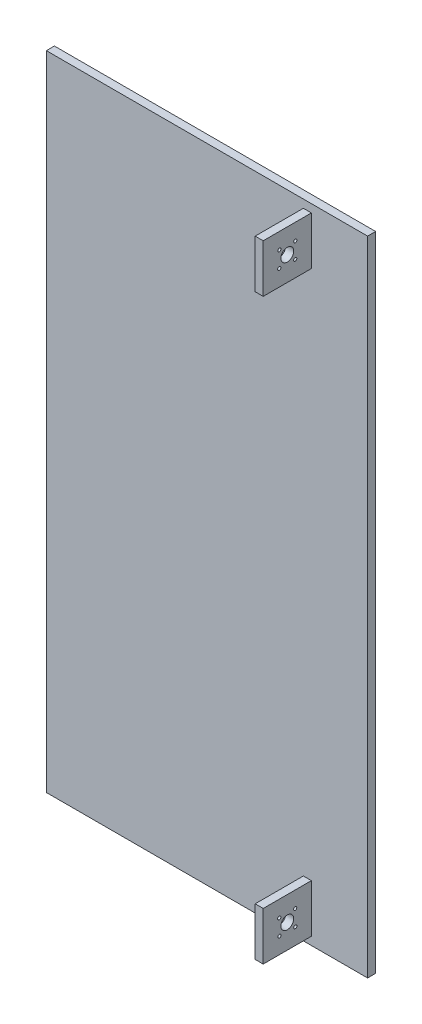
SolidWorks part; units mm, degrees
ref_plane "Plan de face" through (0, 0, 0) normal (0, 0, 1) x (1, 0, 0)
ref_plane "Plan de dessus" through (0, 0, 0) normal (0, 1, 0) x (1, 0, 0)
ref_plane "Plan de droite" through (0, 0, 0) normal (1, 0, 0) x (0, 0, -1)
sketch "Esquisse1" plane through (0, 0, 0) normal (0, 0, 1) x (1, 0, 0)
  line L5 (-100, -200) -> (100, -200)
  line L6 (-100, -200) -> (-100, 200)
  line L11 (-100, 200) -> (100, 200)
  line L12 (100, -200) -> (100, 200)
  line L13 (-100, -200) -> (100, 200) construction
  line L14 (-100, 200) -> (100, -200) construction
  point P0 (0, 0)
  dimension "D1" = 200
  dimension "D2" = 400
extrude "Boss.-Extru.1" add sketch "Esquisse1" along normal blind 5 contours L6 L5 L12 L11
sketch "Esquisse2" plane through (0, 0, 5) normal (0, 0, 1) x (1, 0, 0)
  line L1 (100, -200) -> (100, 200) construction
  line L2 (65, 195) -> (60, 195)
  line L3 (65, 195) -> (65, 165)
  line L4 (65, 165) -> (60, 165)
  line L5 (60, 195) -> (60, 165)
  line L6 (65, 195) -> (60, 165) construction
  line L7 (65, 165) -> (60, 195) construction
  line L8 (-100, 200) -> (100, 200) construction
  point P1 (62.5, 180)
  dimension "D1" = 30
  dimension "D2" = 5
  dimension "D3" = 35
  dimension "D4" = 5
extrude "Boss.-Extru.2" add sketch "Esquisse2" along normal blind 30
sketch "Esquisse3" plane through (65, 0, 0) normal (1, 0, 0) x (0, 0, -1)
  line L1 (-35, 180) -> (-5, 180) construction
  line L2 (-35, 165) -> (-35, 195) construction
  line L3 (-5, 165) -> (-5, 195) construction
  line L4 (-20, 195) -> (-20, 165) construction
  line L5 (-35, 195) -> (-5, 195) construction
  line L6 (-35, 165) -> (-5, 165) construction
  circle A1 centre (-20, 180) radius 4
  dimension "D1" = 8
extrude "Enlèv. mat.-Extru.1" cut sketch "Esquisse3" against normal through all both and the other way through all
sketch "Esquisse4" plane through (60, 0, 0) normal (-1, 0, 0) x (0, 0, 1)
  circle A0 centre (24.9064, 184.9928) radius 1
  circle A2 centre (15.0936, 175.0072) radius 1
  circle A3 centre (24.9928, 175.0936) radius 1
  circle A4 centre (15.0072, 184.9064) radius 1
  dimension "D1" = 2
extrude "Enlèv. mat.-Extru.2" cut sketch "Esquisse4" against normal through all both and the other way through all
mirror "Symétrie1" about plane through (0, 0, 0) normal (0, 1, 0) of "Enlèv. mat.-Extru.2", "Enlèv. mat.-Extru.1", "Boss.-Extru.2"
